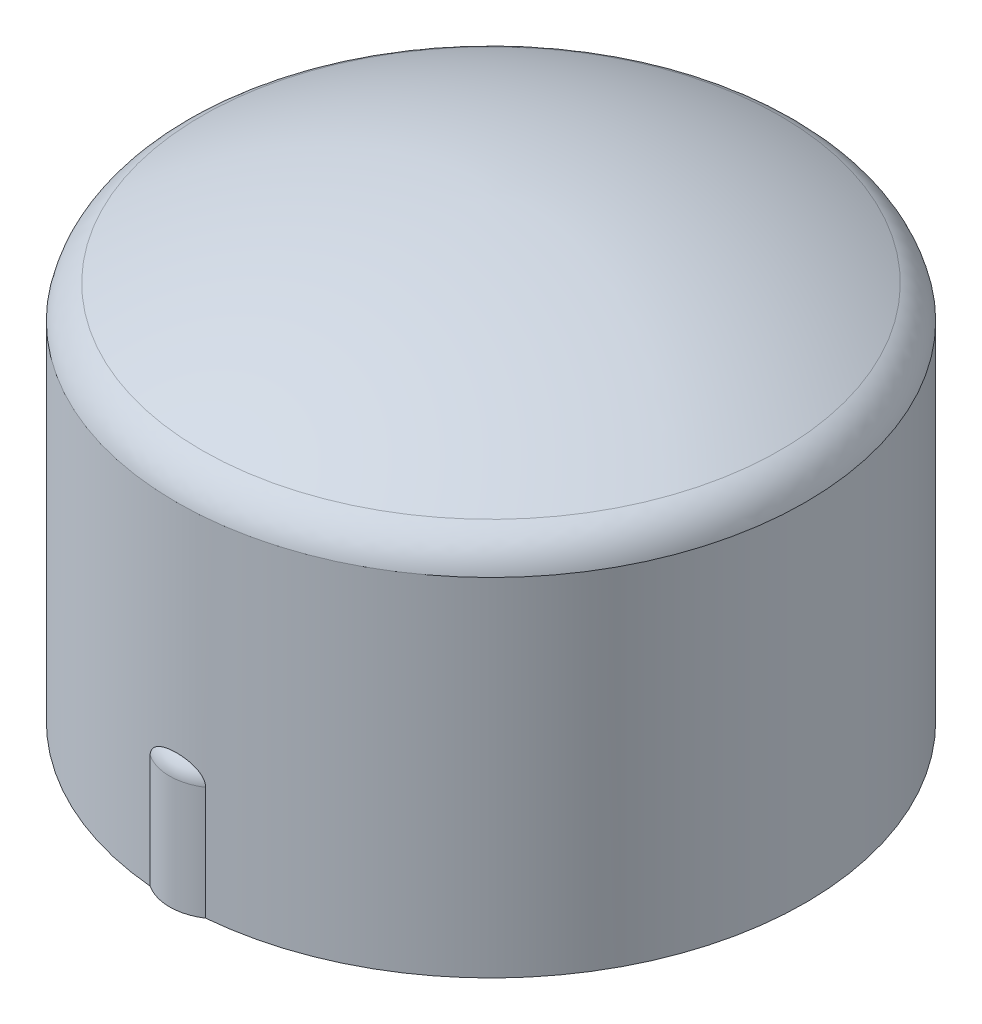
SolidWorks part; units mm, degrees
ref_plane "Front Plane" through (0, 0, 0) normal (0, 0, 1) x (1, 0, 0)
ref_plane "Top Plane" through (0, 0, 0) normal (0, 1, 0) x (1, 0, 0)
ref_plane "Right Plane" through (0, 0, 0) normal (1, 0, 0) x (0, 0, -1)
sketch "Sketch1" plane through (0, 0, 0) normal (1, 0, 0) x (0, 0, -1)
  line L0 (-30.226, 0) -> (-34.544, 0)
  line L1 (-34.544, 0) -> (-34.544, 38.1)
  line L2 (-9.398, 45.2483) -> (-9.398, 42.8999)
  line L3 (-30.226, 38.1) -> (-30.226, 0)
  line L4 (0, 44.5081) -> (0, 50.038)
  line L5 (0, 0) -> (0, 44.5081) construction
  line L7 (0, 50.038) -> (0, 60.1183) construction
  spline S0 degree 2 poles (-34.544, 38.1) (-34.0211, 40.5292) (-31.7933, 41.689) knots 0 0 0 1 1 1
  spline S1 degree 2 poles (-31.7933, 41.689) (-17.0299, 49.7602) (0, 50.038) knots 0 0 0 1 1 1
  spline S2 degree 3 poles (-30.226, 38.1) (-23.6803, 41.8981) (-16.7376, 44.2809) (-9.398, 45.2483) knots 0 0 0 0 0.705521 0.705521 0.705521 0.705521
  spline S3 degree 2 poles (-9.398, 42.8999) (-4.757, 44.0351) (0, 44.5081) knots 0 0 0 1 1 1
  dimension "D1" = 4.318
  dimension "D2" = 38.1
  dimension "D3" = 30.226
  dimension "D4" = 9.398
  dimension "D6" = 3.81
revolve "Revolve1" add sketch "Sketch1" angle 360 about L5
sketch "Sketch2" plane through (0, 0, 0) normal (0, -1, 0) x (1, 0, 0)
  arc A0 (-3.0312, 34.4107) -> (3.0648, 34.4078) centre (0.0145, 29.7601) cw
  circle A1 centre (0, 0) radius 34.544 construction
  spline S0 degree 2 poles (-3.0312, 34.4107) (0.0164, 33.8042) (3.0648, 34.4078) knots 0 0 0 1 1 1
  dimension "D1" = 6.096
extrude "Boss-Extrude1" add sketch "Sketch2" against normal blind 14.986
fillet "Fillet1" radius 2.54 1 edges at (0.0172, 14.986, 35.3193)
fillet "Fillet2" radius 0.508 1 edges at (0, 0, -30.226)
